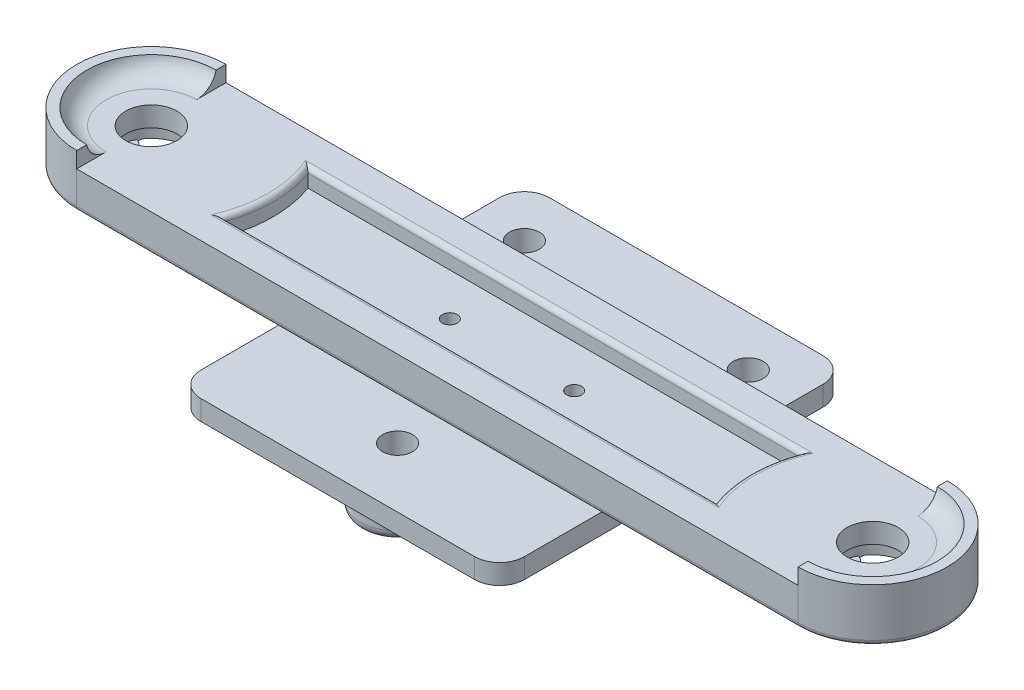
SolidWorks part; units mm, degrees
ref_plane "Alzado" through (0, 0, 0) normal (0, 0, 1) x (1, 0, 0)
ref_plane "Planta" through (0, 0, 0) normal (0, 1, 0) x (1, 0, 0)
ref_plane "Vista lateral" through (0, 0, 0) normal (1, 0, 0) x (0, 0, -1)
sketch "Croquis1" plane through (0, 0, 0) normal (0, 1, 0) x (1, 0, 0)
  line L0 (72.5, 0) -> (-72.5, 0) construction
  line L1 (-72.5, 15) -> (-72.5, -15) construction
  line L2 (-72.5, 0) -> (-80, 12.9904) construction
  line L3 (-72.5, 0) -> (-80, -12.9904) construction
  line L4 (0, 0) -> (0, 15) construction
  line L5 (-72.5, 15) -> (72.5, 15)
  line L6 (-72.5, -15) -> (72.5, -15)
  circle A0 centre (-72.5, 0) radius 15
  circle A2 centre (-72.5, 0) radius 5.15
  circle A3 centre (72.5, 0) radius 15
  circle A4 centre (72.5, 0) radius 5.15
  point P4 (0, 0)
  dimension "D3" = 30
  dimension "D4" = 10.3
  dimension "D1" = 145
  dimension "D2" = 30
  dimension "D5" = 30
  dimension "D6" = 15
extrude "Saliente-Extruir1" add sketch "Croquis1" along normal blind 7.5 contours A0 A2 | L6 A3 L5 A0 | A3 A4 region at (0, 0, 0) region at (-62.1934, 0, -10.3066) region at (82.8066, 0, -10.3066)
sketch "Croquis2" plane through (0, 0, 0) normal (0, -1, 0) x (1, 0, 0)
  line L0 (-72.5, 5.15) -> (-72.5, -5.15) construction
  line L1 (-72.5, 0) -> (-72.5, 5.15) construction
  line L2 (-72.5, 0) -> (-72.5, -5.15) construction
  line L3 (-72.5, 0) -> (-72.5, -5.15) construction
  line L4 (-72.5, 0) -> (-72.5, 5.15) construction
  line L5 (-72.5, 5.15) -> (-72.5, 7.5)
  line L6 (-72.5, 5.15) -> (-72.5, 7.5)
  line L7 (-72.5, -5.15) -> (-72.5, -7.5)
  line L8 (-72.5, -5.15) -> (-72.5, -7.5)
  line L9 (0, 0) -> (0, 15) construction
  line L10 (-72.5, 15) -> (72.5, 15) construction
  line L11 (72.5, -5.15) -> (72.5, -7.5)
  line L12 (72.5, -5.15) -> (72.5, -7.5)
  line L13 (72.5, 5.15) -> (72.5, 7.5)
  line L14 (72.5, 5.15) -> (72.5, 7.5)
  circle A0 centre (-72.5, 0) radius 5.15 construction
  circle A1 centre (-72.5, 0) radius 5.15
  arc A2 (-72.5, 7.5) -> (-72.5, -7.5) centre (-72.5, 0) ccw
  arc A3 (-72.5, -7.5) -> (-72.5, 7.5) centre (-72.5, 0) ccw
  arc A4 (72.5, -7.5) -> (72.5, 7.5) centre (72.5, 0) cw
  circle A5 centre (72.5, 0) radius 5.15
  arc A6 (72.5, 7.5) -> (72.5, -7.5) centre (72.5, 0) cw
  circle M6 centre (-72.5, 0) radius 5.15
  circle M11 centre (72.5, 0) radius 5.15
  dimension "D3" = 15
  dimension "D1" = 0
  dimension "D2" = 0
extrude "Cortar-Extruir1" cut sketch "Croquis2" against normal blind 3.5 contours L6 A2 L7 M6 | L8 A3 L5 M6 | A4 L12 L13 M11 | A6 L14 L11 M11 region at (-77.8177, 0, 0) region at (-72.3323, 0, 6.325) region at (76.2602, 0, -3.7602) region at (72.3323, 0, -6.325)
sketch "Croquis3" plane through (0, 7.5, 0) normal (0, 1, 0) x (1, 0, 0)
  line L0 (-87.5, 0) -> (87.5, 0) construction
  line L1 (-17.5, 25) -> (-23.5102, 25)
  line L2 (-17.5, -25) -> (-23.5102, -25)
  line L3 (0, 0) -> (0, 30) construction
  line L4 (17.5, -25) -> (23.5102, -25)
  line L5 (12.5, -30) -> (-12.5, -30)
  line L6 (17.5, -25) -> (17.5, 25)
  line L7 (12.5, 30) -> (-12.5, 30)
  line L8 (-17.5, -25) -> (-17.5, 25)
  line L9 (17.5, -30) -> (-17.5, 30) construction
  line L10 (17.5, 30) -> (-17.5, -30) construction
  line L11 (17.5, 25) -> (23.5102, 25)
  arc A0 (-72.5, 15) -> (-72.5, -15) centre (-72.5, 0) ccw construction
  arc A1 (72.5, -15) -> (72.5, 15) centre (72.5, 0) ccw construction
  arc A2 (12.5, -30) -> (17.5, -25) centre (12.5, -25) ccw
  arc A3 (-12.5, -30) -> (-17.5, -25) centre (-12.5, -25) cw
  arc A4 (12.5, 30) -> (17.5, 25) centre (12.5, 25) cw
  arc A5 (-12.5, 30) -> (-17.5, 25) centre (-12.5, 25) ccw
  circle A6 centre (-72.5, 0) radius 5.15 construction
  circle A7 centre (-72.5, 0) radius 5.15 construction
  arc A10 (-23.5102, -25) -> (-23.5102, 25) centre (-72.5, 0) ccw
  arc A11 (23.5102, -25) -> (23.5102, 25) centre (72.5, 0) cw
  point P14 (0, 0)
  point P18 (0, 0)
  dimension "D3" = 5
  dimension "D1" = 25
  dimension "D2" = 60
sketch "Croquis9" plane through (0, 7.5, 0) normal (0, 1, 0) x (1, 0, 0)
  line L2 (-72.5, 15) -> (-72.5, 13)
  line L6 (-72.5, -13) -> (-72.5, -15)
  line L7 (72.5, 15) -> (72.5, 13)
  line L8 (-72.5, -15) -> (72.5, -15)
  line L9 (72.5, 15) -> (-72.5, 15)
  line L12 (72.5, -13) -> (72.5, -15)
  arc A5 (-72.5, 13) -> (-72.5, -13) centre (-72.5, 0) ccw
  arc A6 (72.5, -13) -> (72.5, 13) centre (72.5, 0) ccw
  arc A7 (-72.5, 15) -> (-72.5, -15) centre (-72.5, 0) ccw
  arc A8 (72.5, -15) -> (72.5, 15) centre (72.5, 0) ccw
  arc A9 (-72.5, 15) -> (-72.5, -15) centre (-72.5, 0) ccw
  arc A10 (72.5, -15) -> (72.5, 15) centre (72.5, 0) ccw
  dimension "D1" = 0
  dimension "D2" = 2
extrude "Saliente-Extruir6" add sketch "Croquis9" along normal blind 3.2
sketch "Croquis13" plane through (0, 7.5, 0) normal (0, 1, 0) x (1, 0, 0)
  line L0 (0, 0) -> (-47.5, 0) construction
  line L1 (-47.5, 0) -> (-72.5, 0) construction
  line L2 (0, 8) -> (0, -8) construction
  line L3 (48.8146, 8) -> (-48.8146, 8) construction
  line L4 (48.8146, -8) -> (-48.8146, -8) construction
  line L5 (49.5217, -8.5) -> (-49.5217, -8.5)
  line L6 (49.5217, 8.5) -> (-49.5217, 8.5)
  circle A0 centre (-72.5, 0) radius 25 construction
  arc A1 (-48.8146, 8) -> (-48.8146, -8) centre (-72.5, 0) cw construction
  arc A2 (48.8146, 8) -> (48.8146, -8) centre (72.5, 0) ccw construction
  circle A3 centre (-12.5, 0) radius 1.5
  circle A4 centre (12.5, 0) radius 1.5
  arc A5 (-49.5217, 8.5) -> (-49.5217, -8.5) centre (-72.5, 0) cw
  arc A6 (49.5217, 8.5) -> (49.5217, -8.5) centre (72.5, 0) ccw
  circle A7 centre (-72.5, 0) radius 5.15 construction
  circle A8 centre (-72.5, 0) radius 5.15 construction
  point P8 (0, 0)
  point P14 (-12.5, 0)
  dimension "D5" = 3
  dimension "D1" = 12.5
  dimension "D2" = 25
  dimension "D3" = 16
  dimension "D6" = 0.5
extrude "Cortar-Extruir2" cut sketch "Croquis13" against normal blind 3.6
fillet "Redondeo1" radius 4 2 edges at (85.5, 7.5, 0) (-85.5, 7.5, 0)
fillet "Redondeo2" radius 1 4 edges at (0, 0, -15) (87.5, 0, 0) (0, 0, 15) (-87.5, 0, 0)
fillet "Redondeo3" radius 1 4 edges at (0, 7.5, 8.5) (0, 7.5, -8.5) (-48, 7.5, 0) (48, 7.5, 0)
sketch "Croquis14" plane through (0, 0, 0) normal (0, -1, 0) x (1, 0, 0)
  line L2 (-72.5, 7.3837) -> (-72.5, -6.4282) construction
  line L5 (-78.9344, 3.6025) -> (-81.186, 4.2058)
  line L6 (55, 0) -> (-55, 0) construction
  line L7 (-78.9344, -3.6025) -> (-81.186, -4.2058)
  line L8 (-66.0656, -3.6025) -> (-63.814, -4.2058)
  line L9 (-66.0656, 3.6025) -> (-63.814, 4.2058)
  circle A0 centre (-72.5, 0) radius 7.5 construction
  arc A1 (-81.186, 4.2058) -> (-81.186, -4.2058) centre (-73.5, 0) ccw
  circle A4 centre (-72.5, 0) radius 5.15 construction
  circle A5 centre (-72.5, 0) radius 7.5 construction
  arc A6 (-77.5074, 1.2033) -> (-77.5074, -1.2033) centre (-72.5, 0) ccw
  arc A7 (-79.0597, 3.636) -> (-65, 0) centre (-72.5, 0) ccw construction
  arc A9 (-72.5, 14) -> (-72.5, -14) centre (-72.5, 0) ccw construction
  arc A14 (-77.5074, -1.2033) -> (-78.9344, -3.6025) centre (-79.4521, -1.6706) cw
  arc A15 (-77.5074, 1.2033) -> (-78.9344, 3.6025) centre (-79.4521, 1.6706) ccw
  arc A16 (-65.9403, 3.636) -> (-80, 0) centre (-72.5, 0) cw construction
  arc A17 (-67.4926, 1.2033) -> (-66.0656, 3.6025) centre (-65.5479, 1.6706) cw
  arc A18 (-67.4926, -1.2033) -> (-66.0656, -3.6025) centre (-65.5479, -1.6706) ccw
  arc A19 (-67.4926, 1.2033) -> (-67.4926, -1.2033) centre (-72.5, 0) cw
  arc A20 (-63.814, 4.2058) -> (-63.814, -4.2058) centre (-71.5, 0) cw
  point P22 (-76.686, -3)
  point P25 (-76.686, 3)
  point P37 (-68.314, 3)
  point P38 (-68.314, -3)
  dimension "D4" = 15
  dimension "D3" = 1
  dimension "D5" = 2
  dimension "D2" = 3
  dimension "D1" = 4.5
extrude "Saliente-Extruir7" add sketch "Croquis14" along normal blind 2
fillet "Redondeo5" radius 1 12 edges at (-64.8772, 0, -3.9209) (-64.8772, 0, 3.9209) (-80.1228, 0, 3.9209) (-80.1228, 0, -3.9209) (-63.814, -1, -4.2058) (-62.7386, -2, 0) (-63.814, -1, 4.2058) (-62.7386, 0, 0) (-81.186, -1, 4.2058) (-82.2614, -2, 0) (-81.186, -1, -4.2058) (-82.2614, 0, 0)
mirror "Simetría1" about plane through (0, 0, 0) normal (1, 0, 0) of "Redondeo5", "Saliente-Extruir7"
sketch "Croquis15" plane through (0, 0, 0) normal (0, 1, 0) x (1, 0, 0)
  line L0 (-27.5, 35) -> (27.5, 35)
  line L1 (-32.5, 30) -> (-32.5, -30)
  line L2 (-27.5, -35) -> (27.5, -35)
  line L3 (32.5, 30) -> (32.5, -30)
  line L4 (-32.5, 35) -> (32.5, -35) construction
  line L5 (-32.5, -35) -> (32.5, 35) construction
  line L6 (-41.7921, -18) -> (39.3982, -18) construction
  line L7 (-19, -26.6458) -> (-19, -30.8)
  line L12 (-19, -9.3542) -> (-19, -5.2)
  line L13 (-21.2, -3) -> (-21.8, -3)
  line L14 (-24, -9.3542) -> (-24, -5.2)
  line L15 (-21.2, -33) -> (-21.8, -33)
  line L16 (-24, -26.6458) -> (-24, -30.8)
  line L23 (0, -7.0384) -> (0, 7.0384) construction
  line L24 (21.2, -3) -> (21.8, -3)
  line L25 (19, -9.3542) -> (19, -5.2)
  line L26 (24, -9.3542) -> (24, -5.2)
  line L27 (19, -26.6458) -> (19, -30.8)
  line L28 (21.2, -33) -> (21.8, -33)
  line L29 (24, -26.6458) -> (24, -30.8)
  line L30 (2.5, 10.1542) -> (2.5, 6)
  line L31 (2.5, 27.4458) -> (2.5, 31.6)
  line L32 (0.3, 33.8) -> (-0.3, 33.8)
  line L33 (-2.5, 27.4458) -> (-2.5, 31.6)
  line L34 (0.3, 3.8) -> (-0.3, 3.8)
  line L35 (-2.5, 10.1542) -> (-2.5, 6)
  line L36 (-12.2667, 18.8) -> (11.0918, 18.8) construction
  arc A0 (-27.5, 35) -> (-32.5, 30) centre (-27.5, 30) ccw
  arc A1 (27.5, 35) -> (32.5, 30) centre (27.5, 30) cw
  arc A2 (27.5, -35) -> (32.5, -30) centre (27.5, -30) ccw
  arc A3 (-32.5, -30) -> (-27.5, -35) centre (-27.5, -30) ccw
  arc A6 (-24, -9.3542) -> (-30.5, -18) centre (-21.5, -18) ccw
  circle A7 centre (-21.5, -6.5) radius 1
  arc A8 (-19, -5.2) -> (-21.2, -3) centre (-21.2, -5.2) ccw
  arc A9 (-21.8, -3) -> (-24, -5.2) centre (-21.8, -5.2) ccw
  arc A10 (-30.5, -18) -> (-24, -26.6458) centre (-21.5, -18) ccw
  circle A11 centre (-21.5, -29.5) radius 1
  arc A12 (-19, -30.8) -> (-21.2, -33) centre (-21.2, -30.8) cw
  arc A13 (-21.8, -33) -> (-24, -30.8) centre (-21.8, -30.8) cw
  arc A14 (-19, -26.6458) -> (-19, -9.3542) centre (-21.5, -18) ccw
  arc A24 (19, -5.2) -> (21.2, -3) centre (21.2, -5.2) cw
  arc A25 (21.8, -3) -> (24, -5.2) centre (21.8, -5.2) cw
  circle A26 centre (21.5, -6.5) radius 1
  arc A27 (19, -26.6458) -> (19, -9.3542) centre (21.5, -18) cw
  circle A28 centre (21.5, -29.5) radius 1
  arc A29 (19, -30.8) -> (21.2, -33) centre (21.2, -30.8) ccw
  arc A30 (21.8, -33) -> (24, -30.8) centre (21.8, -30.8) ccw
  arc A31 (30.5, -18) -> (24, -26.6458) centre (21.5, -18) cw
  arc A32 (24, -9.3542) -> (30.5, -18) centre (21.5, -18) cw
  arc A33 (-2.5, 27.4458) -> (-2.5, 10.1542) centre (0, 18.8) ccw
  arc A34 (2.5, 31.6) -> (0.3, 33.8) centre (0.3, 31.6) ccw
  arc A35 (-0.3, 33.8) -> (-2.5, 31.6) centre (-0.3, 31.6) ccw
  circle A36 centre (0, 30.3) radius 1
  arc A37 (2.5, 6) -> (0.3, 3.8) centre (0.3, 6) cw
  arc A38 (-0.3, 3.8) -> (-2.5, 6) centre (-0.3, 6) cw
  arc A39 (2.5, 10.1542) -> (2.5, 27.4458) centre (0, 18.8) ccw
  circle A40 centre (0, 7.3) radius 1
  point P0 (0, 0)
  point P41 (-21.5, -3)
  point P79 (0, 33.8)
  point P91 (0, 3.8)
  dimension "D2" = 5
  dimension "D7" = 9
  dimension "D9" = 2.2
  dimension "D14" = 2
  dimension "D1" = 65
  dimension "D3" = 6
  dimension "D4" = 11.5
  dimension "D8" = 11.5
  dimension "D10" = 5
  dimension "D11" = 3.5
  dimension "D12" = 17
  dimension "D13" = 11
  dimension "D15" = 70
extrude "Saliente-Extruir8" add sketch "Croquis15" against normal blind 4 contours L1 A3 L2 A2 L3 A1 L0 A0 A14 L7 A12 L15 A13 L16 A10 A6 L14 A9 L13 A8 L12 L30 L26 A32 A31 L29 A30 L28 A29 L27 A27 L25 A24 L24 A25 | A32 L26 A25 L24 A24 L25 A27 L27 A29 L28 A30 L29 A31 A28 A26 | L7 A14 L12 A8 L13 A9 L14 A6 A10 L16 A13 L15 A12 A11 A7 | L30 | L30 A39 L31 A34 L32 A35 L33 A33 L35 A38 L34 A37 A36 A40 | A28 | A26 | A40 | A36 | A7 | A11 region at (0, 0, -1.4907) region at (-21.5, 0, 18) region at (21.5, 0, 18) region at (0, 0, -18.8) region at (-21.5, 0, 6.5) region at (-21.5, 0, 29.5) region at (21.5, 0, 6.5) region at (21.5, 0, 29.5) region at (0, 0, -30.3) region at (0, 0, -7.3)
extrude "Cortar-Extruir3" cut sketch "Croquis13<2>" against normal through all contours A3 | A4 region at (-12.5, 7.5, 0) region at (12.5, 7.5, 0)
sketch "Croquis13<2>" plane through (0, 7.5, 0) normal (0, 1, 0) x (1, 0, 0) same geometry as "Croquis13"
sketch "Croquis16" plane through (0, -4, 0) normal (0, -1, 0) x (1, 0, 0)
  line L0 (-27.5, 35) -> (27.5, 35) construction
  line L1 (-27.5, -35) -> (27.5, -35) construction
  circle A0 centre (0, 23) radius 7.5
  circle A1 centre (0, 23) radius 3
  circle A2 centre (-22.5, -25) radius 7.5
  circle A3 centre (-22.5, -25) radius 3
  point P3 (0, 0)
  point P5 (0, 27.4978)
  point P11 (-17.3276, -18.785)
  dimension "D1" = 15
  dimension "D2" = 6
  dimension "D4" = 15
  dimension "D3" = 12
  dimension "D5" = 22.5
  dimension "D6" = 10
extrude "Saliente-Extruir9" add sketch "Croquis16" along normal blind 8 contours A0 A1 region at (-7.2879, -4, 23)
extrude "Saliente-Extruir10" add sketch "Croquis16<3>" along normal blind 8 contours A2 A3 region at (-29.7879, -4, -25)
sketch "Croquis16<3>" plane through (0, -4, 0) normal (0, -1, 0) x (1, 0, 0) same geometry as "Croquis16"
ref_plane "Plano1" through (0, 0, 23) normal (0, 0, 1) x (1, 0, 0)
sketch "Croquis17" plane through (0, 0, 23) normal (0, 0, 1) x (1, 0, 0)
  line L0 (5.125, -9.5) -> (-5.125, -9.5)
  line L1 (-7.5, -12) -> (7.5, -12) construction
  arc A0 (-5.125, -9.5) -> (5.125, -9.5) centre (0, -9.5) ccw
  point P6 (0, 0)
  dimension "D1" = 5.125
  dimension "D2" = 2.5
ref_plane "Plano2" through (0, 0, -25) normal (0, 0, -1) x (-1, 0, 0)
sketch "Croquis18" plane through (0, 0, -25) normal (0, 0, -1) x (-1, 0, 0)
  line L0 (27.625, -9.5) -> (17.375, -9.5)
  line L1 (15, -12) -> (30, -12) construction
  line L2 (15, -12) -> (30, -12) construction
  arc A0 (17.375, -9.5) -> (27.625, -9.5) centre (22.5, -9.5) ccw
  point P3 (22.9037, -5.4918)
  point P6 (22.5, -12)
  dimension "D1" = 5.125
  dimension "D2" = 2.5
revolve "Cortar-Revolución1" cut sketch "Croquis17" angle 360 about L0
revolve "Cortar-Revolución2" cut sketch "Croquis18" angle 360 about L0 region at (-22.5, -10.7228, -25) region at (-22.5, -13.0771, -25)
extrude "Cortar-Extruir4" cut sketch "Croquis16<4>" against normal through all contours A1 | A3 region at (0, -4, 23) region at (-22.5, -4, -25)
sketch "Croquis16<4>" plane through (0, -4, 0) normal (0, -1, 0) x (1, 0, 0) same geometry as "Croquis16"
mirror "Simetría2" about plane through (0, 0, 0) normal (1, 0, 0) of "Cortar-Revolución2", "Saliente-Extruir10"
fillet "Redondeo6" radius 2 6 edges at (22.5, -4, -32.5) (22.5, -12, -32.5) (-22.5, -4, -17.5) (-22.5, -12, -32.5) (0, -12, 15.5) (0, -4, 30.5)
sketch "Croquis19" plane through (0, -4, 0) normal (0, -1, 0) x (1, 0, 0)
  circle A1 centre (22.5, -25) radius 3
  circle A2 centre (22.5, -25) radius 3
  dimension "D1" = 0
extrude "Cortar-Extruir5" cut sketch "Croquis19" against normal through all
